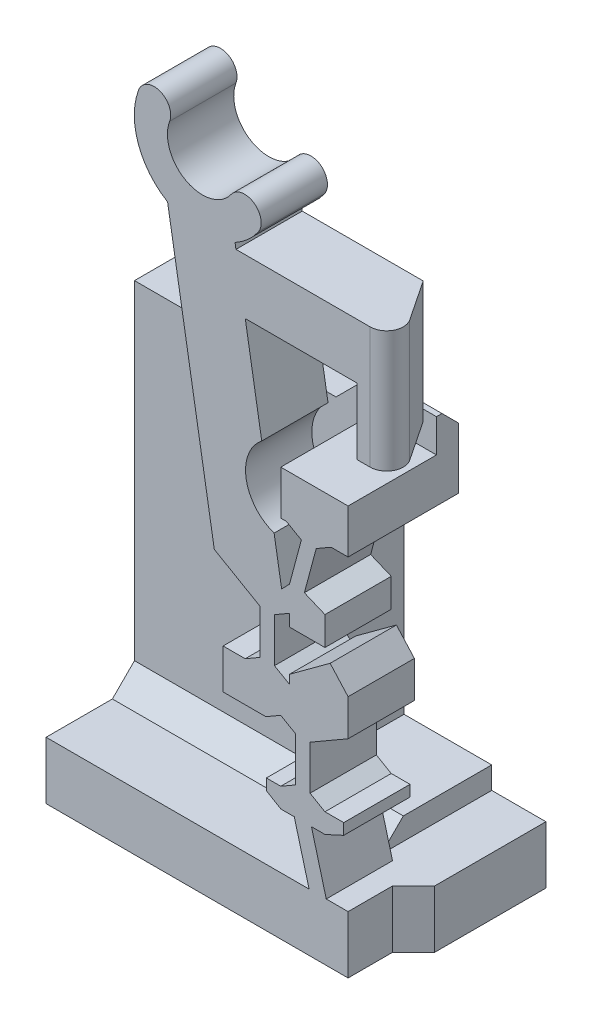
SolidWorks part; units mm, degrees
material "Nylon 6/12"
ref_plane "Front Plane" through (0, 0, 0) normal (0, 0, 1) x (1, 0, 0)
ref_plane "Top Plane" through (0, 0, 0) normal (0, 1, 0) x (1, 0, 0)
ref_plane "Right Plane" through (0, 0, 0) normal (1, 0, 0) x (0, 0, -1)
sketch "Sketch-SkeletonConfigUp" plane through (0, 0, 0) normal (0, 0, 1) x (1, 0, 0)
  line L0 (0, 0) -> (0, -50000) construction
  line L1 (0, 0) -> (4.5811, 6.2164) construction
  line L2 (9.8143, 13.3177) -> (4.5811, 13.945) construction
  line L3 (4.5811, 13.945) -> (2.9713, 10.4094) construction
  line L4 (2.9713, 10.4094) -> (4.5811, 6.2164) construction
  line L5 (4.5811, 13.945) -> (6.2429, 19.1409) construction
  line L6 (2.9713, 10.4094) -> (0.0405, 27.8193) construction
  line L7 (4.5811, 6.2164) -> (9.8143, 13.3177) construction
  line L8 (-587.3593, -797.0242) -> (9.8143, 13.3177) construction
  dimension "D2" = 7.7221
  dimension "D3" = 8.8212
  dimension "D4" = 5.2707
  dimension "D5" = 119.553
  dimension "D6" = 3.8848
  dimension "D7" = 5.4552
  dimension "D8" = 17.6549
  dimension "D9" = 4.4914
  dimension "D10" = 6.745
  dimension "D11" = 145.964
  dimension "D12" = 143.612
sketch "Sketch-SkeletonConfigDown" plane through (0, 0, 0) normal (0, 0, 1) x (1, 0, 0)
  line L0 (0, 0) -> (0, -50000) construction
  line L1 (0, 0) -> (4.5811, 6.2164) construction
  line L2 (9.8143, 13.3177) -> (4.5811, 13.945) construction
  line L3 (4.5811, 13.945) -> (6.1909, 10.4094) construction
  line L4 (6.1909, 10.4094) -> (4.5811, 6.2164) construction
  line L5 (4.5811, 13.945) -> (1.753, 18.6098) construction
  line L6 (6.1909, 10.4094) -> (-8.8652, 19.6294) construction
  line L7 (4.5811, 6.2164) -> (9.8143, 13.3177) construction
  line L8 (-589.9357, -800.5203) -> (9.8143, 13.3177) construction
  dimension "D2" = 7.7221
  dimension "D3" = 8.8212
  dimension "D4" = 5.2707
  dimension "D5" = 119.553
  dimension "D6" = 3.8848
  dimension "D7" = 5.4552
  dimension "D8" = 17.6549
  dimension "D9" = 4.4914
  dimension "D10" = 6.745
  dimension "D11" = 145.964
  dimension "D1" = 143.612
ref_plane "Plane-Cam Base" through (9.128, 0, 0) normal (1, 0, 0) x (0, 0, -1)
ref_plane "Plane-Down-to-Up Derailleur Clearance" through (6.628, 0, 0) normal (1, 0, 0) x (0, 0, -1)
ref_plane "Plane-Cam Cavity Roof" through (5.128, 0, 0) normal (1, 0, 0) x (0, 0, -1)
sketch "Sketch-SwitchBossUp" plane through (0, 0, 0) normal (0, 0, 1) x (1, 0, 0)
  line L0 (3.5811, 11.4759) -> (3.5811, 12.945) construction
  line L5 (5.5811, 12.5552) -> (5.5811, 11.263)
  line L7 (1.5115, 25.1048) -> (1.5536, 24.8548)
  line L8 (-0.4607, 24.7728) -> (1.6966, 11.9577) construction
  line L9 (2.9713, 10.4094) -> (0.0405, 27.8193) construction
  line L11 (0.1364, 21.2256) -> (2.1086, 21.5576) construction
  line L15 (6.628, -23.7286) -> (6.628, 23.7286) construction
  line L16 (2.9713, 10.4094) -> (4.5811, 6.2164) construction
  line L17 (3.5811, 12.945) -> (3.5811, 14.945) construction
  line L18 (5.5811, 12.945) -> (5.5811, 14.945) construction
  line L19 (4.2561, 13.945) -> (4.9061, 13.945) construction
  line L20 (3.5811, 14.945) -> (5.5811, 14.945) construction
  line L21 (3.5811, 12.945) -> (5.5811, 12.945) construction
  line L22 (4.5811, 12.945) -> (4.5811, 14.945) construction
  line L23 (4.5811, 6.2164) -> (8.5405, 7.1023) construction
  line L24 (1.9713, 9.4094) -> (1.9713, 11.4094) construction
  line L25 (3.9713, 9.4094) -> (3.9713, 11.4094) construction
  line L26 (3.9713, 9.4094) -> (1.9713, 9.4094) construction
  line L27 (1.9713, 11.4094) -> (3.9713, 11.4094) construction
  line L28 (3.5811, 7.2164) -> (5.5811, 7.2164) construction
  line L29 (3.5811, 7.2164) -> (3.5811, 5.2164) construction
  line L30 (5.5811, 7.2164) -> (5.5811, 5.2164) construction
  line L31 (3.5811, 5.2164) -> (5.5811, 5.2164) construction
  line L32 (4.9061, 6.2164) -> (4.2561, 6.2164) construction
  line L40 (3.2963, 10.4094) -> (2.6463, 10.4094) construction
  line L66 (0.0405, 27.8193) -> (0.0405, 50027.8193) construction
  line L75 (4.5811, 3.937) -> (5.251, 1.437) construction
  line L76 (5.5811, 11.263) -> (5.5811, 12.5552) construction
  line L77 (5.5811, 7.6061) -> (6.628, 8.2105)
  line L80 (5.8152, 10.763) -> (6.628, 9.8603)
  line L81 (9.128, 1033.2419) -> (9.128, 20.0586) construction
  line L85 (6.9307, 9.5241) -> (8.5405, 7.7363) construction
  line L88 (5.7256, 17.3347) -> (6.628, 17.3347)
  line L92 (3.7762, 8.3129) -> (6.9307, 9.5241) construction
  line L98 (1.9713, 9.0197) -> (0.9713, 9.0197)
  line L99 (0.9713, 9.0197) -> (0.9713, 7.2164)
  line L100 (0.9713, 7.2164) -> (2.9061, 7.2164)
  line L101 (4.5811, 6.2164) -> (6.9307, 9.5241) construction
  line L103 (0.0405, 27.8193) -> (1.9448, 26.4638) construction
  line L104 (6.9307, 9.5241) -> (8.5405, 7.7363) construction
  line L107 (1.9713, 9.4094) -> (1.9713, 9.0197) construction
  line L109 (0.0405, 27.8193) -> (-2.1498, 28.6358) construction
  line L111 (6.628, 9.8603) -> (6.628, 8.2105)
  line L112 (6.628, 9.8603) -> (6.9307, 9.5241) construction
  line L113 (2.9306, 4.8267) -> (2.9306, 4.3267)
  line L114 (7.3693, 7.7363) -> (7.3563, 7.7363) construction
  line L121 (5.6392, -1.0859) -> (5.6392, 1.437) construction
  line L122 (9.028, 22.3548) -> (9.028, 19.3548)
  line L127 (5.5811, 15.3347) -> (5.5811, 14.945) construction
  line L133 (2.9713, 10.4094) -> (6.1909, 10.4094) construction
  line L134 (4.5811, 10.4094) -> (4.5811, 13.945) construction
  line L135 (4.5811, 10.4094) -> (4.5811, 6.2164) construction
  line L137 (3.9713, 9.4094) -> (5.5811, 7.2164) construction
  line L139 (5.8152, 10.763) -> (3.9713, 9.4094)
  line L142 (3.0345, 1.437) -> (3.0345, -1.1653)
  line L143 (9.128, 20.0586) -> (9.128, 18.3333) construction
  line L145 (9.128, 16.6071) -> (9.128, -49992.4167) construction
  line L147 (5.5811, 11.263) -> (5.5811, 12.5552) construction
  line L150 (3.0345, -1.1653) -> (6.628, -1.1653)
  line L151 (4.1929, 3.937) -> (4.9694, 3.937) construction
  line L152 (4.5126, 14.945) -> (3.9767, 12.945)
  line L153 (5.1855, 14.945) -> (4.6496, 12.945)
  line L157 (3.5811, 17.3347) -> (3.5811, 15.3347)
  line L158 (5.8605, 15.3347) -> (6.628, 15.3347)
  line L162 (3.2963, 11.4094) -> (3.2963, 9.4094)
  line L164 (2.6463, 11.4094) -> (2.6463, 9.4094)
  line L169 (4.2561, 7.2164) -> (4.2561, 5.2164)
  line L170 (4.9061, 5.2164) -> (4.9061, 7.2164)
  line L175 (4.2561, 7.2164) -> (3.5811, 7.6061)
  line L176 (4.9061, 7.2164) -> (5.5811, 7.6061)
  line L177 (5.5811, 7.2164) -> (5.5811, 7.6061) construction
  line L179 (4.2561, 5.2164) -> (3.5811, 4.8267)
  line L180 (3.5811, 5.2164) -> (3.5811, 4.8267) construction
  line L181 (3.5811, 4.8267) -> (2.9306, 4.8267)
  line L183 (4.9061, 5.2164) -> (5.5811, 4.8267)
  line L184 (5.5811, 5.2164) -> (5.5811, 4.8267) construction
  line L186 (9.128, -23.7286) -> (9.128, 23.7286) construction
  line L187 (2.6463, 9.4094) -> (1.9713, 9.0197)
  line L188 (3.2963, 9.4094) -> (3.9713, 9.0197)
  line L189 (3.2963, 11.4094) -> (3.9713, 11.7991)
  line L190 (2.6463, 11.4094) -> (1.6966, 11.9577)
  line L191 (3.9713, 11.4094) -> (3.9713, 11.7991) construction
  line L192 (3.9713, 11.7991) -> (3.9713, 11.263)
  line L193 (4.6496, 12.945) -> (5.5811, 12.5552)
  line L194 (3.9767, 12.945) -> (3.6203, 12.5779)
  line L195 (3.9713, 11.263) -> (5.5811, 11.263)
  line L196 (3.9713, 9.4094) -> (3.9713, 9.0197)
  line L197 (3.5811, 7.2164) -> (3.5811, 7.6061) construction
  line L199 (3.5811, 7.6061) -> (2.9061, 7.2164)
  line L201 (2.9306, 4.3267) -> (2.9306, 3.937) construction
  line L202 (2.9306, 3.937) -> (4.1929, 3.937) construction
  line L205 (4.1929, 3.937) -> (3.585, 3.937)
  line L207 (9.128, 18.3333) -> (9.128, 16.6071) construction
  line L208 (6.628, -1.1653) -> (6.628, 1.437)
  line L209 (9.128, 20.0586) -> (9.128, 16.6071) construction
  line L211 (5.6392, 1.437) -> (4.9694, 3.937)
  line L212 (4.8628, 1.437) -> (4.1929, 3.937)
  line L214 (4.5126, 14.945) -> (3.8375, 15.3347)
  line L215 (3.8375, 15.3347) -> (3.5811, 15.3347)
  line L216 (5.1855, 14.945) -> (5.8605, 15.3347)
  line L217 (5.5811, 12.945) -> (5.5811, 12.5552) construction
  line L218 (5.1855, 14.945) -> (5.1855, 15.3347) construction
  line L219 (5.8605, 15.3347) -> (3.8375, 15.3347) construction
  line L221 (9.028, 22.3548) -> (9.028, 24.8548)
  line L224 (3.5811, 17.3347) -> (5.7256, 17.3347)
  line L232 (6.628, 15.3347) -> (6.628, 17.3347)
  line L236 (1.5536, 24.8548) -> (9.028, 24.8548)
  line L240 (4.9694, 3.937) -> (5.5824, 3.937)
  line L241 (5.5824, 3.937) -> (6.4306, 4.3267)
  line L248 (7.028, 22.3548) -> (1.9744, 22.3548)
  line L249 (1.9744, 22.3548) -> (2.7198, 17.9273)
  line L250 (9.028, 19.3548) -> (7.028, 19.3548)
  line L251 (7.028, 19.3548) -> (7.028, 22.3548)
  line L252 (3.2801, 14.5986) -> (3.6203, 12.5779)
  line L253 (4.2672, 14.0291) -> (4.895, 13.8608) construction
  line L254 (5.6392, 1.437) -> (4.8628, 1.437) construction
  line L255 (4.8628, 1.437) -> (3.0345, 1.437) construction
  line L256 (4.5811, 6.2164) -> (4.5811, 3.937) construction
  line L257 (4.8628, 1.437) -> (3.0345, 1.437)
  line L259 (5.6392, 1.437) -> (6.628, 1.437)
  line L260 (3.585, 3.937) -> (2.9306, 4.3267)
  line L261 (1.6966, 11.9577) -> (0.5733, 12.6062)
  line L262 (0.5733, 12.6062) -> (-1.5413, 25.1678)
  line L367 (5.5811, 4.8267) -> (6.4306, 4.8267)
  line L368 (6.4306, 4.8267) -> (6.4306, 4.3267)
  arc A0 (1.5115, 25.1048) -> (2.5558, 26.0289) centre (0.0405, 27.8193) ccw
  arc A1 (-1.5413, 25.1678) -> (-2.8525, 28.8978) centre (0.0405, 27.8193) cw
  arc A2 (-2.8525, 28.8978) -> (-1.447, 28.3738) centre (-2.1498, 28.6358) cw
  arc A3 (2.5558, 26.0289) -> (1.3338, 26.8987) centre (1.9448, 26.4638) ccw
  arc A4 (-1.447, 28.3738) -> (1.3338, 26.8987) centre (0.0405, 27.8193) ccw
  arc A5 (3.5811, 12.945) -> (3.5811, 14.945) centre (3.1778, 13.945) ccw construction
  arc A6 (5.5811, 12.945) -> (5.5811, 14.945) centre (5.9843, 13.945) cw construction
  arc A7 (2.528, 9.9183) -> (1.9713, 11.4094) centre (1.568, 10.4094) ccw construction
  arc A8 (3.9713, 11.4094) -> (3.9713, 9.4094) centre (4.3745, 10.4094) ccw construction
  arc A9 (3.5811, 7.2164) -> (3.5811, 5.2164) centre (3.1779, 6.2164) cw construction
  arc A10 (5.5811, 7.2164) -> (5.5811, 5.2164) centre (5.9844, 6.2164) ccw construction
  circle A28 centre (0.0405, 27.8193) radius 2.3375 construction
  arc A29 (1.9713, 9.4094) -> (2.528, 9.9183) centre (1.568, 10.4094) ccw construction
  arc A30 (3.2801, 14.5986) -> (2.7198, 17.9273) centre (3.9114, 16.4164) cw
  arc A31 (-0.4607, 24.7728) -> (-1.5413, 25.1678) centre (0.0405, 27.8193) cw construction
  point P53 (4.5811, 13.945)
  point P63 (2.9713, 10.4094)
  point P93 (1.1225, 21.3916)
  dimension "D23" = 1.5875
  dimension "D24" = 0.75
  dimension "D2" = 2
  dimension "D5" = 2
  dimension "D8" = 42
  dimension "D16" = 42
  dimension "D27" = 120
  dimension "D28" = 120
  dimension "D29" = 120
  dimension "D30" = 120
  dimension "D31" = 120
  dimension "D32" = 120
  dimension "D33" = 120
  dimension "D34" = 120
  dimension "D17" = 0.5
  dimension "D21" = 2
  dimension "D38" = 2
  dimension "D39" = 0.5
  dimension "D40" = 60
  dimension "D41" = 1
  dimension "D42" = 45
  dimension "D43" = 120
  dimension "D10" = 15
  dimension "D25" = 15
  dimension "D26" = 120
  dimension "D35" = 120
  dimension "D83" = 3.5
  dimension "D14" = 2.5
  dimension "D15" = 0.25
  dimension "D7" = 3
  dimension "D9" = 2
  dimension "D6" = 0.65
  dimension "D13" = 18.5
  dimension "D18" = 2.5
  dimension "D19" = 0.65
  dimension "D20" = 1
  dimension "D12" = 0.75
extrude "Boss-Switch Body" add sketch "Sketch-SwitchBossUp" along normal blind 3
sketch "Sketch1" plane through (0, 0, 0) normal (0, 0, -1) x (-1, 0, 0)
  line L1 (-7.5811, -1.1653) -> (0.4122, -1.1653)
  line L2 (-7.5811, -1.1653) -> (-7.5811, 1.437)
  line L4 (0.4122, -1.1653) -> (0.4122, 1.437)
  line L5 (-3.5811, 18.8347) -> (-7.5811, 18.8347)
  line L10 (-7.5811, 18.8347) -> (-7.5811, 15.3347)
  line L11 (-4.8628, 1.437) -> (-5.6392, 1.437)
  line L12 (-7.5811, 15.3347) -> (-3.5811, 15.3347)
  line L13 (-4.8628, 1.437) -> (-3.0345, 1.437)
  line L14 (-3.5811, 15.3347) -> (-3.5811, 18.8347)
  line L20 (-4.9694, 3.937) -> (-5.6392, 1.437) construction
  line L22 (-3.0345, -1.1653) -> (-6.628, -1.1653) construction
  line L23 (-3.0345, 1.437) -> (0.4122, 1.437)
  line L24 (-5.6392, 1.437) -> (-6.628, 1.437)
  line L25 (-6.628, 1.437) -> (-7.5811, 1.437)
  dimension "D1" = 3.5
extrude "Boss-Flange Width" add sketch "Sketch1" along normal blind 5
ref_plane "Plane-Sta2Sit Groove" through (0.0405, 0, 0) normal (1, 0, 0) x (0, 0, -1)
ref_plane "Plane-Cam Outer Surface" through (-12.0395, 0, 0) normal (1, 0, 0) x (0, 0, -1)
ref_plane "Plane-FlangeTop" through (-7.0395, 0, 0) normal (1, 0, 0) x (0, 0, -1)
sketch "Sketch2" plane through (-7.0395, 0, 0) normal (1, 0, 0) x (0, 0, -1)
  line L0 (5, 15.3347) -> (-3, 15.3347) construction
  line L1 (5, 17.3347) -> (1, 17.3347)
  line L2 (5, 17.3347) -> (5, 15.3347)
  line L3 (5, 15.3347) -> (1, 15.3347)
  line L4 (1, 17.3347) -> (1, 15.3347)
  line L5 (-3, -1.1653) -> (-3, 1.437) construction
  line L11 (5, 1.437) -> (-3, 1.437)
  line L12 (5, 1.437) -> (5, -1.1653)
  line L13 (5, -1.1653) -> (-3, -1.1653)
  line L14 (-3, 1.437) -> (-3, -1.1653)
  line L15 (0, 10.4094) -> (0, 27.8193) construction
  line L17 (5, 1.437) -> (5, -1.1653) construction
  line L18 (-3, 1.437) -> (0, 1.437) construction
  dimension "D1" = 1
  dimension "D2" = 2
extrude "Boss-Flange Height" add sketch "Sketch2" along normal up to surface (11.6675 mm away)
sketch "Sketch10" plane through (0, 15.3347, 0) normal (0, 1, 0) x (1, 0, 0)
  line L0 (9.128, -23.7286) -> (9.128, 23.7286) construction
  line L1 (7.5811, 5) -> (5.128, 5)
  line L2 (7.5811, 5) -> (7.5811, 2)
  line L3 (7.5811, 2) -> (5.128, 2)
  line L5 (4.628, 7) -> (4.628, 1) construction
  line L6 (3.5811, 1) -> (-7.0395, 1) construction
  line L8 (5.128, 5) -> (5.128, 2)
  dimension "D1" = 1
  dimension "D2" = 0.5
  dimension "D3" = 4.5
extrude "Cut-Up-To-Down Derailleur Clearance" cut sketch "Sketch10" along normal up to next
sketch "Sketch17" plane through (0, 15.3347, 0) normal (0, -1, 0) x (1, 0, 0)
  line L0 (5.128, -5) -> (-7.0395, -5)
  line L1 (5.128, -5) -> (-7.0395, -5) construction
  line L2 (-7.0395, -5) -> (-7.0395, -1)
  line L3 (-7.0395, -1) -> (5.128, -1)
  line L4 (5.128, -1) -> (5.128, -5)
  line L5 (-7.0395, -1) -> (-7.0395, -5) construction
extrude "Boss-Flange Support" add sketch "Sketch17" along normal up to surface (13.8977 mm away) up to face at (3.5343, 1.437, 0.2)
sketch "Sketch-HolePositions" plane through (0, -1.1653, 0) normal (0, -1, 0) x (1, 0, 0)
  line L0 (-7.0395, -3) -> (7.5811, -3) construction
  line L1 (7.5811, -5) -> (-7.0395, -5) construction
  line L2 (7.5811, -5) -> (7.5811, 0) construction
  line L4 (-7.0395, -22.2167) -> (-7.0395, 22.2167) construction
  point P6 (-5.0395, -3)
  point P7 (-0.5395, -3)
  dimension "D1" = 2
  dimension "D2" = 4.5
  dimension "D3" = 2
sketch "Sketch6" plane through (0, -1.1653, 0) normal (0, -1, 0) x (-1, 0, 0)
  point P0 (5.0395, 3)
  point P3 (0.5395, 3)
hole_wizard "Tap Drill for M2x0.4 Tap1" positions "Sketch6" profile "Sketch5" hole size "M2x0.4" standard "ANSI Metric" end condition through all
sketch "Sketch5" plane through (-5.0395, -1.1653, -3) normal (1, 0, 0) x (0, 0, -1)
  line L0 (0, 0) -> (0, 30.5511)
  line L1 (0, 30.5511) -> (0.8, 30.5511)
  line L2 (0.8, 30.5511) -> (0.8, 0)
  line L5 (0.8, 0) -> (0, 0)
  line L11 (0, -6.35) -> (0, 107.95) construction
  dimension "Thru Hole Dia." = 1.6
  dimension "Thru Hole Depth" = 30.5511
sketch "Sketch9" plane through (0, -1.1653, 0) normal (0, -1, 0) x (1, 0, 0)
  point P0 (-5.0395, -3)
  point P3 (-0.5395, -3)
hole_wizard "M2 Clearance Hole2" positions "Sketch9" profile "Sketch8" hole size "M2" standard "ANSI Metric"
sketch "Sketch8" plane through (-5.0395, -1.1653, -3) normal (1, 0, 0) x (0, 0, -1)
  line L0 (0, 0) -> (0, 15.721)
  line L1 (0, 15.721) -> (1.2, 15)
  line L2 (1.2, 15) -> (1.2, 0)
  line L5 (1.2, 0) -> (0, 0)
  line L10 (0, 15.721) -> (-1.2, 15) construction
  line L11 (0, -6.35) -> (0, 107.95) construction
  dimension "Hole Dia." = 2.4
  dimension "Hole Depth" = 15
  dimension "Drill Angle" = 118
sketch "Sketch-Measurements for Derailleur Ramps" [suppressed] plane through (0, 0, 0) normal (0, 0, 1) x (1, 0, 0)
  line L0 (3.184, 15.1695) -> (2.4687, 19.4188)
  line L1 (2.8264, 17.2941) -> (1.8402, 17.1281)
  line L2 (2.9713, 10.4094) -> (0.0405, 27.8193) construction
  line L3 (1.8402, 17.1281) -> (-1.3081, 15.0016)
  line L4 (6.1909, 10.4094) -> (-8.8652, 19.6294) construction
  line L5 (1.8402, 17.1281) -> (2.6012, 12.6077)
  line L6 (2.6012, 12.6077) -> (-1.3081, 15.0016)
  line L7 (0.2661, 16.0649) -> (0.2661, 17.1281)
  line L8 (0.2661, 17.1281) -> (1.8402, 17.1281)
  line L9 (6.1909, 10.4094) -> (2.9713, 10.4094)
  line L10 (5.386, 8.3129) -> (3.7762, 8.3129)
  line L11 (2.6116, 18.5698) -> (1.5115, 25.1048) construction
  line L12 (6.1909, 10.4094) -> (4.5811, 6.2164) construction
  line L13 (4.5811, 8.3129) -> (4.5811, 8.7912)
  line L14 (4.5811, 6.2164) -> (5.386, 8.3129)
  line L15 (2.9713, 10.4094) -> (4.5811, 6.2164) construction
  line L16 (3.7762, 8.3129) -> (4.5811, 6.2164)
  line L17 (5.386, 8.3129) -> (5.386, 8.7912)
  dimension "D1" = 1.5742
  dimension "D2" = 0.8049
ref_plane "Plane1" through (0, 7.1023, 0) normal (0, 1, 0) x (1, 0, 0)
ref_plane "Plane-Cantilever Cut" [suppressed] through (7.0848, 8.5204, -1.9058) normal (-0.6301, -0.7578, 0.1695) x (-0.7765, 0.6151, -0.1368)
sketch "Sketch14" [suppressed] plane through (7.0848, 8.5204, -1.9058) normal (-0.6301, -0.7578, 0.1695) x (-0.7765, 0.6151, -0.1368)
  line L0 (2.3023, -1.6911) -> (-0.3551, -1.6911)
  line L2 (2.3023, -4.3362) -> (2.3023, -1.6911)
  line L3 (-0.3551, -1.6911) -> (-0.3551, -4.4608)
  line L5 (-0.3551, -4.4608) -> (1.0087, -5.0843)
  line L6 (1.0087, -5.0843) -> (2.3023, -4.3362)
extrude "Cut-Down-to-Up Cantilever Slope" [suppressed] cut sketch "Sketch14" against normal up to next
ref_plane "Plane-Symmetry Plane" through (0, 0, 1.5) normal (0, 0, 1) x (1, 0, 0)
sketch "Sketch-Cable Center Point" plane through (0, 0, 1.5) normal (0, 0, 1) x (1, 0, 0)
  line L0 (0.0405, 27.8193) -> (0.1722, 27.0366)
  line L1 (2.9713, 10.4094) -> (0.0405, 27.8193) construction
  point P0 (0.0405, 27.8193)
  dimension "D1" = 0.7937
chamfer "Chamfer-Flange Support" distance 1.5 angle 45 1 edges at (3.5811, 17.3347, -3)
chamfer "Chamfer-Flange Support 2" distance 1.5 angle 45 2 edges at (5.128, 17.0847, -2) (5.128, 15.3347, -1.5)
chamfer "Chamfer-Flange Support 3" distance 1 angle 45 1 edges at (-0.9558, 1.437, -1)
chamfer "Chamfer7" [suppressed] distance 1 angle 45
sketch "Sketch23" plane through (0, 0, -1) normal (0, 0, 1) x (1, 0, 0)
  line L0 (5.128, 2.437) -> (1.1605, 2.437)
  line L1 (-7.0395, 2.437) -> (5.128, 2.437) construction
  line L2 (1.1605, 2.437) -> (1.1605, 13.8347)
  line L3 (1.1605, 13.8347) -> (5.128, 13.8347)
  line L4 (5.128, 13.8347) -> (5.128, 2.437)
  line L5 (0.6605, -1.1653) -> (0.6605, 13.8347) construction
  dimension "D1" = 0.5
extrude "Cut-Gap for Printing" cut sketch "Sketch23" against normal through all
sketch "Sketch25" plane through (0, 0, 0) normal (0, 0, 1) x (1, 0, 0)
  line L0 (6.628, 15.3347) -> (7.5811, 15.3347)
  line L1 (7.5811, 15.3347) -> (7.5811, 18.8347)
  line L2 (7.5811, 18.8347) -> (6.628, 18.8347)
  line L3 (6.628, -23.7286) -> (6.628, 23.7286) construction
  line L4 (7.5811, 18.8347) -> (3.5811, 18.8347) construction
  line L5 (6.628, 18.8347) -> (6.628, 15.3347)
  line L6 (7.5811, 18.8347) -> (7.5811, 15.3347) construction
extrude "Cut-Derailleur Clearance" cut sketch "Sketch25" against normal through all
chamfer "Chamfer8" distance 1 angle 45 1 edges at (6.628, 0.1359, 0)
ref_plane "Plane2" through (4.8655, 0, -3.2437) normal (-0.8321, 0, 0.5547) x (0.5547, 0, 0.8321)
sketch "Sketch26" plane through (4.8655, 0, -3.2437) normal (-0.8321, 0, 0.5547) x (0.5547, 0, 0.8321)
  line L0 (8.7768, 24.8548) -> (8.7768, 19.0593)
  line L1 (5.0078, 24.8548) -> (0.8618, 24.8548) construction
  line L3 (8.7768, 19.0593) -> (2.8692, 19.0593)
  line L4 (2.8692, 19.0593) -> (2.8692, 24.8548)
  line L5 (2.8692, 24.8548) -> (8.7768, 24.8548)
extrude "Cut-Up-to-Down Cantilever Slope" cut sketch "Sketch26" against normal up to next
sketch "Sketch27" plane through (5.128, 0, 0) normal (1, 0, 0) x (0, 0, -1)
  line L0 (3.5, 18.8347) -> (3.5, 13.8347) construction
  line L1 (2.5, 18.8347) -> (5, 18.8347)
  line L2 (2.5, 18.8347) -> (2.5, 13.8347)
  line L3 (2.5, 13.8347) -> (5, 13.8347)
  line L4 (5, 18.8347) -> (5, 13.8347)
  dimension "D1" = 1
extrude "Cut-Wide Derailleur Clearance" cut sketch "Sketch27" against normal blind 4 and the other way through all
chamfer "Chamfer9" distance 1.25 angle 45 1 edges at (4.8545, 18.8347, -2.5)
sketch "Sketch28" plane through (0, 0, -1) normal (0, 0, 1) x (1, 0, 0)
  line L0 (3.5811, 18.8347) -> (6.628, 18.8347)
  line L1 (6.628, 18.8347) -> (6.628, 17.3347)
  line L2 (6.628, 17.3347) -> (3.5811, 17.3347)
  line L3 (3.5811, 17.3347) -> (3.5811, 18.8347)
extrude "Cut-Extrude1" cut sketch "Sketch28" along normal up to surface (1 mm away) up to face at (5.1045, 18.0847, 0)
fillet "Fillet1" radius 0.75 1 edges at (9.028, 22.1048, 3)
equation "\"axle-diameter\"=2"
equation "\"switch-thickness\"=12"
equation "\"base-width\"=4.0"
equation "\"axle-bushing-radius\"=3"
equation "\"clearance\"= 0.25"
equation "\"arm-width\"=1.5"
equation "\"min-diameter\"=70"
equation "\"alpha\"=143.6120"
equation "\"gamma\"=119.5526"
equation "\"delta\"=145.9637"
equation "\"epsilon\"=6.7452"
equation "\"l_AB\"=8.8212"
equation "\"l_AC\"=4.4914"
equation "\"l_BD\"=5.2707"
equation "\"l_CD\"=3.8848"
equation "\"l_CE\"=17.6549"
equation "\"l_DF\"=5.4552"
equation "\"l_OA\"=7.7221"
equation "\"D2@Sketch-SkeletonConfigUp\" = \"l_OA\""
equation "\"D3@Sketch-SkeletonConfigUp\" = \"l_AB\""
equation "\"D4@Sketch-SkeletonConfigUp\" = \"l_BD\""
equation "\"D5@Sketch-SkeletonConfigUp\" = \"gamma\""
equation "\"D6@Sketch-SkeletonConfigUp\" = \"l_CD\""
equation "\"D7@Sketch-SkeletonConfigUp\" = \"l_DF\""
equation "\"D8@Sketch-SkeletonConfigUp\" = \"l_CE\""
equation "\"D9@Sketch-SkeletonConfigUp\" = \"l_AC\""
equation "\"D_groove\"=3.175"
equation "\"D7@Sketch-SkeletonConfigDown\" = \"l_DF\""
equation "\"D6@Sketch-SkeletonConfigDown\" = \"l_CD\""
equation "\"D2@Sketch-SkeletonConfigDown\" = \"l_OA\""
equation "\"D3@Sketch-SkeletonConfigDown\" = \"l_AB\""
equation "\"D9@Sketch-SkeletonConfigDown\" = \"l_AC\""
equation "\"D8@Sketch-SkeletonConfigDown\" = \"l_CE\""
equation "\"D5@Sketch-SkeletonConfigDown\" = \"gamma\""
equation "\"D4@Sketch-SkeletonConfigDown\" = \"l_BD\""
equation "\"D1@Sketch-SkeletonConfigDown\" = \"alpha\""
equation "\"hinge_length\"=1.5"
equation "\"hinge_depth\"=0.25"
equation "\"D10@Sketch-SkeletonConfigUp\"=\"epsilon\""
equation "\"D11@Sketch-SkeletonConfigUp\"=\"delta\""
equation "\"D12@Sketch-SkeletonConfigUp\"=\"alpha\""
equation "\"D11@Sketch-SkeletonConfigDown\"=\"delta\""
equation "\"D10@Sketch-SkeletonConfigDown\"=\"epsilon\""
equation "\"EE_dx\"=8.9056"
equation "\"EE_dy\"=8.1898"
equation "\"r_groove\"=\"D_groove\"/2"
equation "\"t_wall\"=25.4/16"
equation "\"width_lower\"=\"D_groove\"+\"t_wall\""
equation "\"cable_to_bottom\"=30.6257"
equation "\"switch_EE-up_base_dy\"=24"
equation "\"switch_EE-down_base_dy\"=16"
equation "\"D_axle\"=25.4/8"
equation "\"D_up_to_down\"=16"
equation "\"D_down_to_up\"=25"
equation "\"t_cam_base\"=7.5"
equation "\"D23@Sketch-SwitchBossUp\"=\"D_groove\"/2"
equation "\"D1@Sketch-Cable Center Point\"=\"D_groove\"/4"
